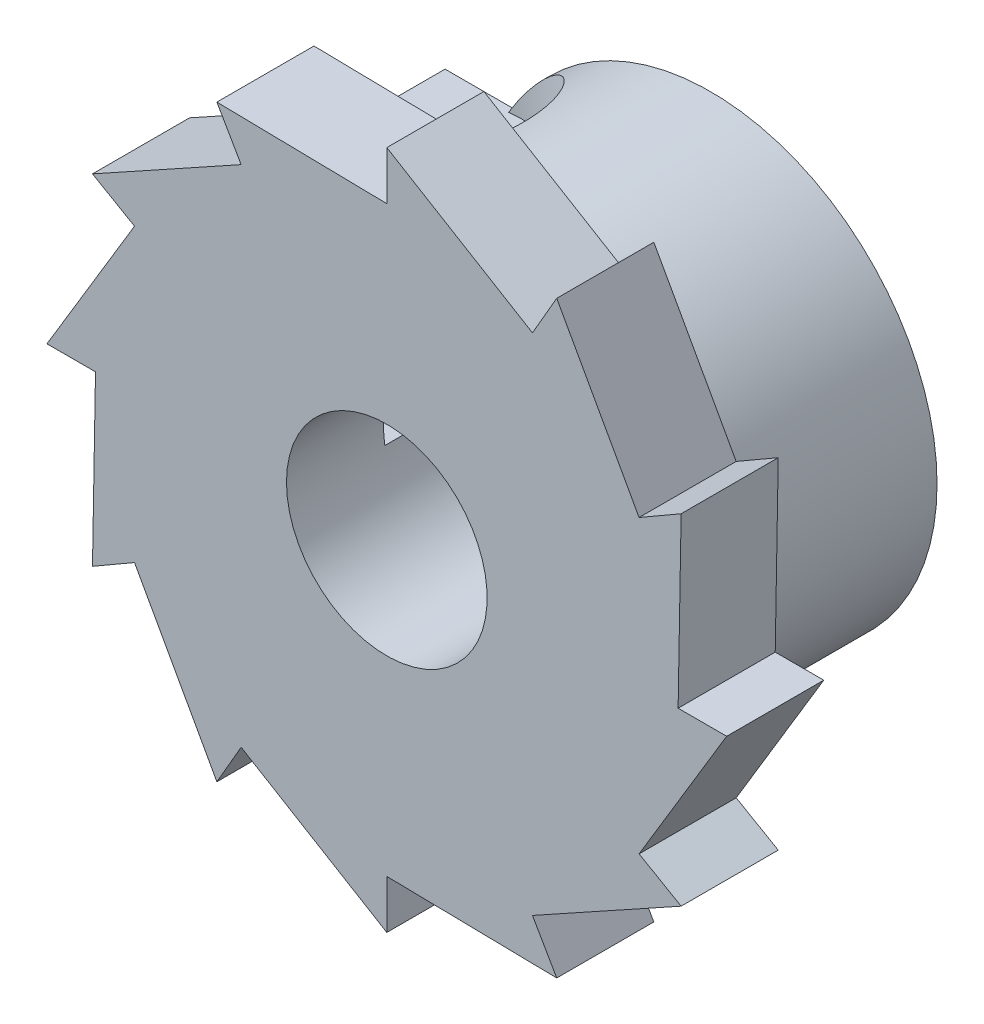
SolidWorks part; units mm, degrees
ref_plane "Front Plane" through (0, 0, 0) normal (0, 0, 1) x (1, 0, 0)
ref_plane "Top Plane" through (0, 0, 0) normal (0, 1, 0) x (1, 0, 0)
ref_plane "Right Plane" through (0, 0, 0) normal (1, 0, 0) x (0, 0, -1)
sketch "Sketch1" plane through (0, 0, 0) normal (0, 0, 1) x (1, 0, 0)
  line L0 (0, 9) -> (0, 10.5)
  line L1 (0.0027, 10.5) -> (-49999.9973, 10.5) construction
  line L2 (0, 0) -> (0, 50000) construction
  line L3 (-0.0178, -0.0309) -> (24999.9822, 43301.2393) construction
  line L4 (0, 9) -> (0, 3.1)
  line L5 (4.5, 7.7942) -> (1.55, 2.6847)
  line L6 (4.5, 7.7942) -> (0, 10.5)
  circle A0 centre (0, 0) radius 9 construction
  circle A1 centre (0, 0) radius 3.1 construction
  arc A2 (0, 10.5) -> (4.5, 7.7942) centre (0, 5.4051) cw construction
  arc A3 (0, 3.1) -> (1.55, 2.6847) centre (0, 0) cw
  dimension "D1" = 6.2
  dimension "D2" = 18
  dimension "D3" = 30
  dimension "D4" = 1.5
extrude "Boss-Extrude1" add sketch "Sketch1" along normal blind 3
pattern_circular "CirPattern1" count 12 over 360 about axis through (0, 0, 3) along (0, 0, -1) of "Boss-Extrude1"
sketch "Sketch3" plane through (0, 0, 0) normal (0, 0, -1) x (-1, 0, 0)
  line L0 (7, -3.5) -> (7, -7)
  line L2 (-7, 0) -> (-7, 7)
  line L3 (-7, 7) -> (7, 7)
  line L5 (7, -7) -> (0, -7)
  line L7 (8.2, 3.5) -> (8.2, -3.5)
  line L8 (8.2, -3.5) -> (7, -3.5)
  line L9 (7, 0) -> (50007, 0) construction
  line L10 (7, 7) -> (8.2, 7)
  line L11 (8.2, 7) -> (8.2, 3.5)
  arc A0 (7, 0) -> (0, -7) centre (0, 0) ccw construction
  arc A1 (0, -7) -> (-7, 0) centre (0, 0) cw
  circle A2 centre (0, 0) radius 3.1
  circle A3 centre (0, 0) radius 3.1 construction
  point P14 (8.2, 0)
  dimension "D1" = 14
  dimension "D2" = 8.2
extrude "Boss-Extrude2" add sketch "Sketch3" along normal blind 7
sketch "Sketch4" plane through (0, 7, 0) normal (0, 1, 0) x (1, 0, 0)
  line L0 (-3.1, 0) -> (3.1, 0) construction
  line L1 (-3.1, 0) -> (3.1, 0) construction
  line L2 (-3.1, 0) -> (-3.1, -50000) construction
  line L3 (-8.2, 0) -> (-5.9339, 0) construction
  line L4 (-8.2, 3.75) -> (-3.1, 3.75) construction
  circle A1 centre (-5.65, 3.75) radius 1.35
  point P8 (0, 0)
  point P9 (-5.65, 3.75)
  point P10 (0, 0)
  point P11 (0, 0)
  dimension "D1" = 2.7
  dimension "D2" = 3.75
sketch "Sketch6" plane through (-8.2, 0, 0) normal (-1, 0, 0) x (0, 0, 1)
  line L0 (0, 0) -> (-50000, 0) construction
  line L1 (-7, -0.5) -> (-7, 0.5)
  line L2 (-7, -7) -> (-7, -3.5) construction
  line L3 (-7, 0.5) -> (0, 0.5)
  line L10 (-7, -0.5) -> (0, -0.5)
  line L11 (0, -3.5) -> (0, 3.8252) construction
  line L12 (0, 0.5) -> (0, -0.5)
  point P12 (-0.5, 0)
  dimension "D4" = 0.5
sketch "Sketch9" plane through (0, 7, 0) normal (0, 1, 0) x (1, 0, 0)
  circle A0 centre (-5.65, 3.75) radius 1.75
  point P0 (-5.65, 3.75)
  dimension "D1" = 3.5
extrude "Cut-Extrude19" cut sketch "Sketch6" against normal blind 12.5
extrude "Cut-Extrude20" cut sketch "Sketch9" against normal up to surface (6.5 mm away) up to face at (-5.6297, 0.5, -3.5)
sketch "Sketch12" plane through (0, 0, -7) normal (0, 0, -1) x (-1, 0, 0)
  line L0 (0, 0) -> (50000, 0) construction
  line L1 (8.2, -3.5) -> (6.0622, -3.5) construction
  line L2 (0, -7) -> (7, -7) construction
  line L3 (8.2, 3.5) -> (6.0622, 3.5)
  line L4 (0, -7) -> (7, -7)
  line L5 (7, -7) -> (7, -3.5)
  line L6 (7, -3.5) -> (6.0622, -3.5)
  line L7 (8.2, 3.5) -> (8.2, 7)
  line L8 (8.2, 7) -> (-7, 7)
  line L9 (-7, 7) -> (-7, 0)
  arc A0 (0, -7) -> (6.0622, -3.5) centre (0, 0) ccw
  arc A1 (6.0622, 3.5) -> (-7, 0) centre (0, 0) ccw
  line M9 (8.2, 0.5) -> (8.2, 7)
  line M10 (8.2, 7) -> (-7, 7)
  line M11 (-7, 7) -> (-7, 0)
  line M13 (0, -7) -> (7, -7)
  line M14 (7, -7) -> (7, -3.5)
sketch "Sketch13" plane through (0, 7, 0) normal (0, 1, 0) x (1, 0, 0)
  line L0 (0, 0) -> (0, 50000) construction
  line L1 (-8.2, 7) -> (-8.2, 0) construction
  line L2 (0, 0) -> (-8.2, 0)
  line L3 (0, 0) -> (0, 0.5)
  line L4 (0, 0.5) -> (-8.2, 0.5)
  line L5 (-8.2, 0) -> (-8.2, 0.5)
  dimension "D1" = 0.5
extrude "Cut-Extrude24" cut sketch "Sketch13" against normal up to surface (6.5 mm away) up to face at (-5.65, 0.5, -2)
sketch "Sketch14" plane through (0, -7, 0) normal (0, -1, 0) x (1, 0, 0)
  circle A0 centre (-5.65, -3.75) radius 3.1
  point P0 (-5.65, -3.75)
  dimension "D1" = 6.2
sketch "Sketch15" plane through (0, 7, 0) normal (0, 1, 0) x (1, 0, 0)
  circle A0 centre (-5.65, 3.75) radius 3.1 construction
  circle A1 centre (-5.65, 3.75) radius 3.1
extrude "Cut-Extrude29" cut sketch "Sketch12" against normal up to surface (7 mm away) contours A1 L8 M11 | A1 L3 M9 M10 | A0 L6 M13 M14 region at (5.4364, 5.4364, -7) region at (-6.0019, 5.597, -7) region at (-5.2918, -5.7512, -7) up to face at (-4.0579, 2.8574, 0)
extrude "Cut-Extrude30" cut sketch "Sketch4" against normal through all
extrude "Cut-Extrude31" cut sketch "Sketch15" against normal up to surface (3.5 mm away) up to face at (-6.9978, 3.5, -3.75)
extrude "Cut-Extrude32" cut sketch "Sketch14" against normal up to surface (3.5 mm away) up to face at (-6.9311, -3.5, -3.5833)
equation "\"ratchetTeethCount\"= 12"
equation "\"D3@Sketch1\"=360/\"ratchetTeethCount\""
equation "\"D1@CirPattern1\"=\"ratchetTeethCount\""
equation "\"ratchetHeight\"=1.5"
equation "\"D4@Sketch1\"=\"ratchetHeight\""
equation "\"ratchetInnerDiameter\"= 18"
equation "\"D2@Sketch1\"=\"ratchetInnerDiameter\""
